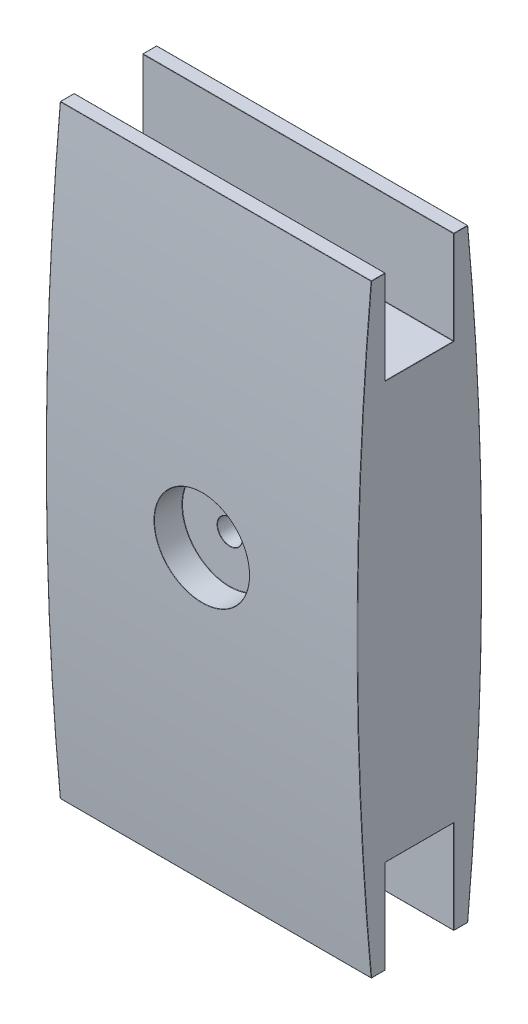
SolidWorks part; units mm, degrees
ref_plane "Front Plane" through (0, 0, 0) normal (0, 0, 1) x (1, 0, 0)
ref_plane "Top Plane" through (0, 0, 0) normal (0, 1, 0) x (1, 0, 0)
ref_plane "Right Plane" through (0, 0, 0) normal (1, 0, 0) x (0, 0, -1)
sketch "Sketch2" plane through (0, 0, 0) normal (1, 0, 0) x (0, 0, -1)
  line L0 (0, 97) -> (0, -97) construction
  line L1 (-20, -97) -> (20, -97) construction
  line L2 (-20, -97) -> (-20, 97) construction
  line L3 (-20, 97) -> (20, 97) construction
  line L4 (20, -97) -> (20, 97) construction
  line L5 (-20, -97) -> (20, 97) construction
  line L6 (-20, 97) -> (20, -97) construction
  line L7 (-20, 0) -> (20, 0) construction
  line L8 (-11, 97) -> (11, 97) construction
  line L9 (-11, 97) -> (-11, 67)
  line L10 (-11, 67) -> (11, 67)
  line L11 (11, 97) -> (11, 67)
  line L12 (-11, 97) -> (11, 67) construction
  line L13 (-11, 67) -> (11, 97) construction
  line L14 (-11, -97) -> (-11, -67)
  line L15 (11, -97) -> (11, -67)
  line L16 (-11, -67) -> (11, -67)
  line L17 (-20, 97) -> (-11, 97) construction
  line L18 (11, 97) -> (20, 97) construction
  line L19 (-20, -97) -> (-11, -97) construction
  line L20 (11, -97) -> (20, -97) construction
  line L21 (-15.5, 97) -> (-11, 97)
  line L22 (11, 97) -> (15.5, 97)
  line L23 (-15.5, -97) -> (-11, -97)
  line L24 (11, -97) -> (15.5, -97)
  arc A0 (-15.5, 97) -> (-15.5, -97) centre (1027.6944, 0) ccw
  arc A1 (15.5, 97) -> (15.5, -97) centre (-1027.6944, 0) cw
  point P0 (0, 0)
  point P8 (0, 82)
  point P19 (-15.5, 97)
  point P20 (-15.5, -97)
  dimension "D1" = 40
  dimension "D2" = 134
  dimension "D3" = 22
  dimension "D4" = 30
extrude "Boss-Extrude1" add sketch "Sketch2" along normal blind 100
ref_plane "Plane1" through (0, 0, 20) normal (0, 0, 1) x (1, 0, 0)
sketch "Sketch4" plane through (0, 0, 20) normal (0, 0, 1) x (1, 0, 0)
  line L0 (50, 97) -> (50, -97) construction
  line L4 (0, 97) -> (0, -97)
  line L5 (0, -97) -> (100, -97)
  line L6 (100, -97) -> (100, 97)
  line L7 (100, 97) -> (0, 97)
  line L8 (0, 97) -> (0, -97)
  line L9 (0, -97) -> (100, -97)
  line L10 (100, -97) -> (100, 97)
  line L11 (100, 97) -> (0, 97)
  circle A0 centre (50, 0) radius 15.2786
  dimension "D1" = 0
extrude "Cut-Extrude1" cut sketch "Sketch4" against normal blind 9 contours A0
mirror "Mirror1" about plane through (0, 0, 0) normal (0, 0, 1) of "Cut-Extrude1"
sketch "Sketch5" plane through (0, 0, 20) normal (0, 0, 1) x (1, 0, 0)
  circle A0 centre (50, 0) radius 4
  dimension "D1" = 8
extrude "Cut-Extrude2" cut sketch "Sketch5" against normal through all both and the other way through all
fillet "Fillet1" radius 0.1 42 edges at (50, 97, 11) (50, 97, -11) (50, 67, -11) (50, 67, 11) (54, 0, 11) (65.2786, 0, 11) (50, -97, 11) (50, -97, -11) (50, -67, 11) (50, -67, -11) (100, 97, -13.25) (100, -97, -13.25) (100, -82, -11) (100, -67, 0) (100, -82, 11) (100, -97, 13.25) (100, 97, 13.25) (100, 82, 11) (100, 67, 0) (100, 82, -11) (50, 97, 15.5) (100, 0, 20) (50, -97, 15.5) (35.1306, 3.5125, 19.9941) (65.2786, 0, -11) (46, 0, -11) (64.8694, -3.5125, -19.9941) (50, -97, -15.5) (100, 0, -20) (50, 97, -15.5) (0, 67, 0) (0, 82, 11) (0, 97, 13.25) (0, 0, 20) (0, -97, 13.25) (0, -82, 11) (0, -67, 0) (0, -82, -11) (0, -97, -13.25) (0, 0, -20) (0, 97, -13.25) (0, 82, -11)
